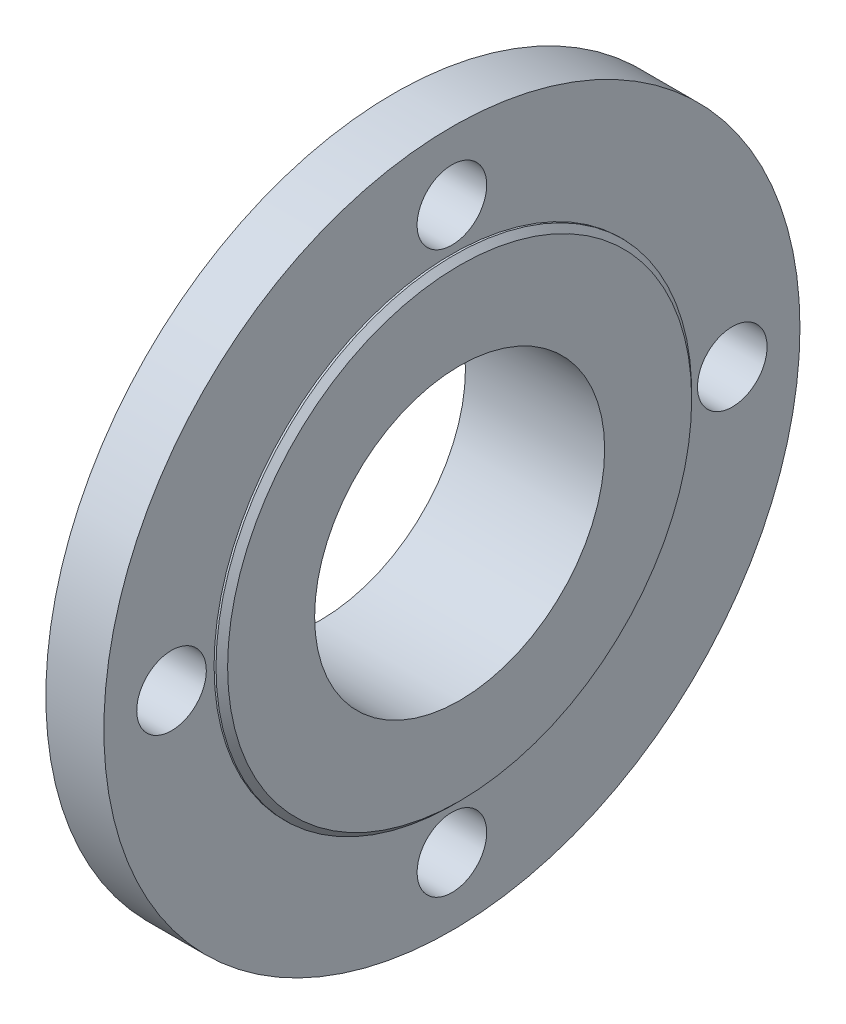
SolidWorks part; units mm, degrees
material "PE Высокой плотности"
ref_plane "Спереди" through (0, 0, 0) normal (0, 0, 1) x (1, 0, 0)
ref_plane "Сверху" through (0, 0, 0) normal (0, 1, 0) x (1, 0, 0)
ref_plane "Справа" through (0, 0, 0) normal (1, 0, 0) x (0, 0, -1)
sketch "Эскиз1" plane through (0, 0, 0) normal (0, 0, 1) x (1, 0, 0)
  line L0 (0, 0) -> (-200, 0) construction
  line L1 (-34, 37.5) -> (0, 37.5)
  line L2 (0, 37.5) -> (0, 90)
  line L3 (0, 90) -> (-15, 90)
  line L4 (-15, 90) -> (-15, 44.7)
  line L6 (-15, 44.7) -> (-34, 44.7)
  line L7 (-34, 44.7) -> (-34, 37.5)
  dimension "R усл" = 37.5
  dimension "R наружный" = 90
  dimension "Толщина" = 15
  dimension "Длина" = 34
  dimension "R площадки" = 44.7
revolve "Повернуть1" add sketch "Эскиз1" angle 360 about L0
ref_axis "Ось1" through (84.0043, 0, 0) along (-1, 0, 0)
sketch "Эскиз2" plane through (0, 0, 0) normal (1, 0, 0) x (0, 0, -1)
  circle A0 centre (0, 72.5) radius 9
  dimension "D2" = 18
  dimension "D1" = 72.5
extrude "Вырез-Вытянуть2" cut sketch "Эскиз2" against normal through all
pattern_circular "Круговой массив2" count 4 over 360 about axis through (84.0043, 0, 0) along (-1, 0, 0) of "Вырез-Вытянуть2"
sketch "Эскиз3" plane through (0, 0, 0) normal (1, 0, 0) x (0, 0, -1)
  circle A0 centre (0, 0) radius 61.5
  circle A1 centre (0, 0) radius 37.5 construction
  circle A2 centre (0, 0) radius 37.5
  dimension "D1" = 123
extrude "Вытянуть1" add sketch "Эскиз3" along normal blind 2
chamfer "Фаска5" distance 1.5 angle 45 1 edges at (2, 0, -61.5)
other "Точка маршрута1"
ref_axis "Ось2" through (5, 0, 0) along (-1, 0, 0)
sketch "Эскиз4" plane through (-34, 0, 0) normal (-1, 0, 0) x (0, 0, 1)
  circle A0 centre (0, 0) radius 37.5 construction
  point P0 (0, 0)
other "Точка соединения1" parameters "Диаметр"=75, "StubLength"=0
ref_axis "Ось3" through (-44, 0, 0) along (1, 0, 0)
equation "\"D1@Эскиз1\"  =(\"R площадки@Эскиз1\"-\"R хвоста@Эскиз1\") * 2.5"
equation "\"D2@Эскиз1\"  =( \"R хвоста@Эскиз1\" - \"R усл@Эскиз1\" )  / 4"
equation "\"D1@Эскиз3\" = 2 * ( \"D1@Эскиз2\" - \"D2@Эскиз2\" / 2 - 2 )"
